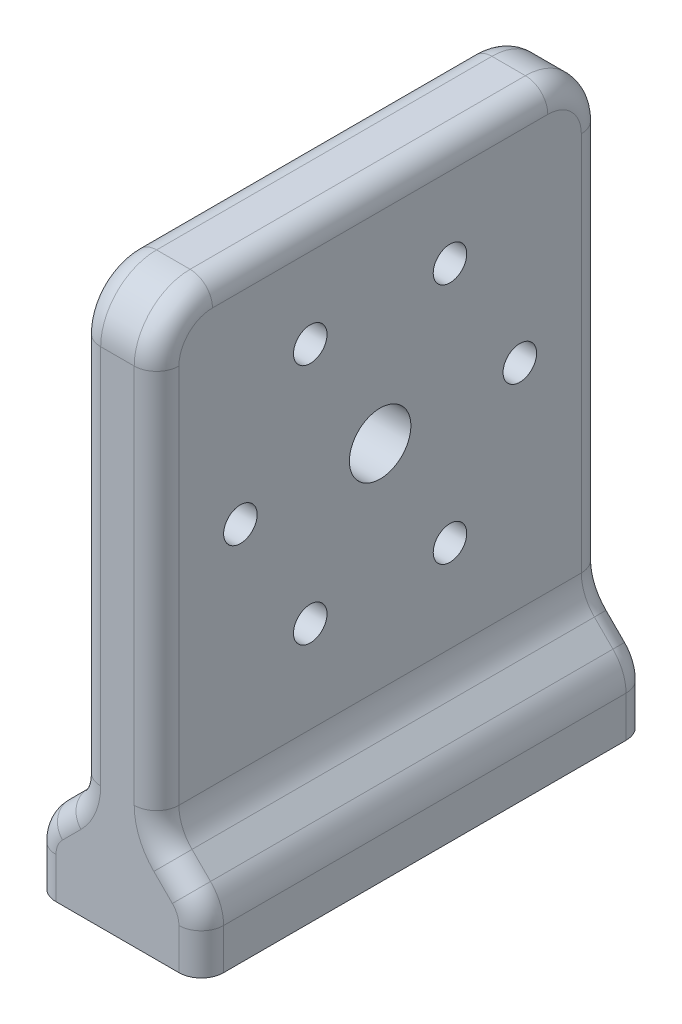
SolidWorks part; units mm, degrees
ref_plane "Front Plane" through (0, 0, 0) normal (0, 0, 1) x (1, 0, 0)
ref_plane "Top Plane" through (0, 0, 0) normal (0, 1, 0) x (1, 0, 0)
ref_plane "Right Plane" through (0, 0, 0) normal (1, 0, 0) x (0, 0, -1)
sketch "Sketch1" plane through (0, 0, 0) normal (0, 1, 0) x (1, 0, 0)
  line L1 (-3.5, 20) -> (3.5, 20)
  line L2 (-3.5, 20) -> (-3.5, -20)
  line L3 (-3.5, -20) -> (3.5, -20)
  line L4 (3.5, 20) -> (3.5, -20)
  line L5 (-3.5, 20) -> (3.5, -20) construction
  line L6 (-3.5, -20) -> (3.5, 20) construction
  point P0 (0, 0)
  dimension "D1" = 7
  dimension "D2" = 40
extrude "Boss-Extrude1" add sketch "Sketch1" along normal blind 50
sketch "Sketch3" plane through (3.5, 0, 0) normal (1, 0, 0) x (0, 0, -1)
  line L0 (-20, 50) -> (-20, 0) construction
  line L1 (20, 0) -> (-20, 0)
  line L2 (20, 0) -> (20, 12.3123)
  line L3 (20, 12.3123) -> (-20, 12.3123)
  line L4 (-20, 0) -> (-20, 12.3123)
extrude "Boss-Extrude2" add sketch "Sketch3" along normal blind 4 and the other way blind 11
chamfer "Chamfer1" distance 7 angle 45 2 edges at (-7.5, 12.3123, 0) (7.5, 12.3123, 0)
fillet "Fillet1" radius 4 4 edges at (7.5, 5.3123, 0) (-7.5, 5.3123, 0) (-3.5, 9.3123, 0) (3.5, 9.3123, 0)
sketch "Sketch4" plane through (0, 0, 0) normal (0, -1, 0) x (1, 0, 0)
  line L0 (3.85, 0) -> (-3.85, 0) construction
  circle A0 centre (0, 10) radius 2
  circle A1 centre (0, -10) radius 2
  dimension "D1" = 4
  dimension "D2" = 10
extrude "Cut-Extrude2" cut sketch "Sketch4" against normal blind 10
sketch "Sketch5" plane through (-3.5, 0, 0) normal (-1, 0, 0) x (0, 0, 1)
  line L0 (20, 50) -> (20, 10.9692) construction
  line L1 (-20, 50) -> (20, 50) construction
  line L2 (20, 0) -> (-20, 0) construction
  circle A0 centre (0, 30) radius 12.5 construction
  circle A1 centre (-12.5, 30) radius 1.5
  circle A2 centre (-6.25, 40.8253) radius 1.5
  circle A3 centre (6.25, 40.8253) radius 1.5
  circle A4 centre (12.5, 30) radius 1.5
  circle A5 centre (6.25, 19.1747) radius 1.5
  circle A6 centre (-6.25, 19.1747) radius 1.5
  circle A7 centre (0, 30) radius 2.75
  dimension "D1" = 25
  dimension "D4" = 3
  dimension "D6" = 5.5
  dimension "D2" = 20
  dimension "D3" = 20
  dimension "D7" = 30
  dimension "D5" = 6
extrude "Cut-Extrude3" cut sketch "Sketch5" against normal through all
fillet "Fillet2" radius 5 2 edges at (0, 50, -20) (0, 50, 20)
fillet "Fillet3" radius 2 26 edges at (7.5, 1.8277, -20) (7.1955, 5.1862, -20) (5.5, 7.3123, -20) (3.8045, 9.4384, -20) (3.5, 27.9846, -20) (3.5, 48.5355, -18.5355) (3.5, 50, 0) (3.5, 48.5355, 18.5355) (7.5, 1.8277, 20) (7.1955, 5.1862, 20) (5.5, 7.3123, 20) (3.8045, 9.4384, 20) (-7.5, 1.8277, -20) (-7.1955, 5.1862, -20) (-5.5, 7.3123, -20) (-3.8045, 9.4384, -20) (-3.5, 27.9846, -20) (-3.5, 48.5355, -18.5355) (-3.5, 50, 0) (-3.5, 48.5355, 18.5355) (-7.5, 1.8277, 20) (-7.1955, 5.1862, 20) (-5.5, 7.3123, 20) (-3.8045, 9.4384, 20) (3.5, 27.9846, 20) (-3.5, 27.9846, 20)
